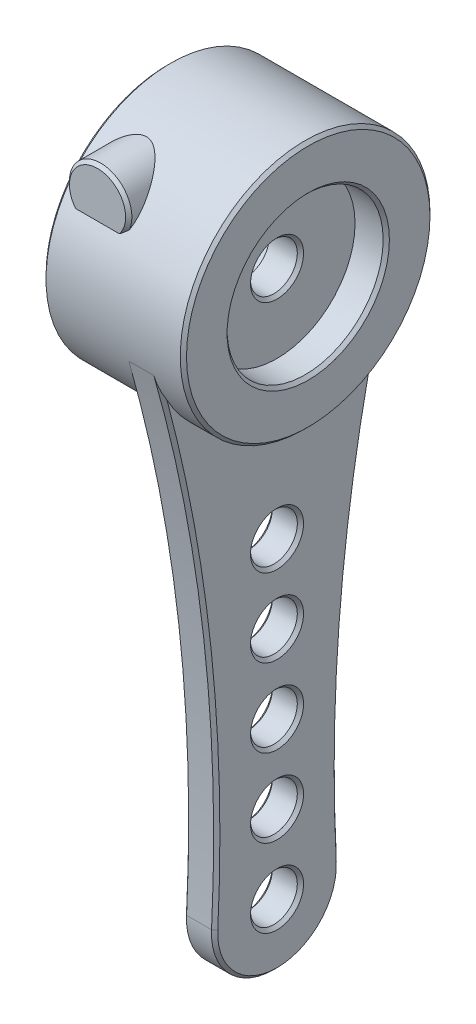
SolidWorks part; units mm, degrees
ref_plane "前视基准面" through (0, 0, 0) normal (0, 0, 1) x (1, 0, 0)
ref_plane "上视基准面" through (0, 0, 0) normal (0, 1, 0) x (1, 0, 0)
ref_plane "右视基准面" through (0, 0, 0) normal (1, 0, 0) x (0, 0, -1)
sketch "草图1" plane through (0, 0, 0) normal (1, 0, 0) x (0, 0, -1)
  circle A0 centre (0, 0) radius 8
  dimension "D1" = 16
extrude "凸台-拉伸1" add sketch "草图1" along normal blind 9
sketch "草图2" plane through (9, 0, 0) normal (1, 0, 0) x (0, 0, -1)
  circle A0 centre (0, 0) radius 5
  dimension "D1" = 10
extrude "切除-拉伸1" cut sketch "草图2" against normal blind 2
sketch "草图3" plane through (7, 0, 0) normal (1, 0, 0) x (0, 0, -1)
  circle A0 centre (0, 0) radius 1.5
  dimension "D1" = 3
extrude "切除-拉伸2" cut sketch "草图3" against normal blind 2
sketch "草图4" plane through (5, 0, 0) normal (1, 0, 0) x (0, 0, -1)
  circle A0 centre (0, 0) radius 3
  dimension "D1" = 6
extrude "切除-拉伸3" cut sketch "草图4" against normal blind 5
sketch "草图6" plane through (0, 0, 0) normal (0, 0, 1) x (1, 0, 0)
  line L0 (0, 8) -> (0, -8) construction
  circle A0 centre (2.5, 5) radius 2
  dimension "D1" = 4
  dimension "D2" = 2.5
  dimension "D3" = 5
extrude "凸台-拉伸2" add sketch "草图6" along normal blind 7
ref_plane "基准面1" through (5, 0, 0) normal (-1, 0, 0) x (0, 0, 1)
sketch "草图7" plane through (5, 0, 0) normal (-1, 0, 0) x (0, 0, 1)
  line L0 (0, 0) -> (0, -35) construction
  arc A0 (-3.9946, -34.7929) -> (3.9946, -34.7929) centre (0, -35) ccw
  arc A1 (-7.6934, -2.1937) -> (-3.9946, -34.7929) centre (-103.8605, -29.6143) cw
  circle A2 centre (0, 0) radius 8 construction
  arc A3 (7.6934, -2.1937) -> (3.9946, -34.7929) centre (103.8605, -29.6143) ccw
  circle A4 centre (0, -35) radius 1.5
  circle A5 centre (0, -30) radius 1.5
  circle A6 centre (0, -25) radius 1.5
  circle A7 centre (0, -20) radius 1.5
  circle A8 centre (0, -15) radius 1.5
  arc A9 (-7.6934, -2.1937) -> (7.6934, -2.1937) centre (0, 0) ccw
  dimension "D1" = 100
  dimension "D2" = 8
  dimension "D3" = 3
  dimension "D5" = 20
  dimension "D6" = 5
  dimension "D7" = 5
  dimension "D8" = 5
  dimension "D4" = 39
extrude "凸台-拉伸3" add sketch "草图7" against normal blind 2
chamfer "倒角1" distance 0.2 angle 45 6 edges at (2.5, 7, 7) (0, 0, -3) (0, 0, -8) (7, 0, -1.5) (9, 0, -5) (9, 0, -8)
chamfer "倒角2" distance 0.2 angle 45 16 edges at (5, -15, 1.5) (5, -20, 1.5) (5, -25, 1.5) (5, -30, 1.5) (5, -35, 1.5) (7, -15, 1.5) (7, -20, 1.5) (7, -25, 1.5) (7, -30, 1.5) (7, -35, 1.5) (5, -18.3405, -4.498) (5, -39, 0) (5, -18.3405, 4.498) (7, -18.3405, -4.498) (7, -39, 0) (7, -18.3405, 4.498)
move or copy body "实体-移动/复制1" [suppressed] bodies to move or copy 111
move or copy body "实体-移动/复制2" [suppressed] bodies to move or copy 112 parameters "D1"=0, "D2"=0, "D3"=0
move or copy body "实体-移动/复制3" [suppressed] bodies to move or copy 113 parameters "D1"=0, "D2"=0, "D3"=0
move or copy body "实体-移动/复制4" [suppressed] bodies to move or copy 114 parameters "D1"=0, "D2"=0, "D3"=0
move or copy body "实体-移动/复制5" [suppressed] bodies to move or copy 115 parameters "D1"=0, "D2"=0, "D3"=0
